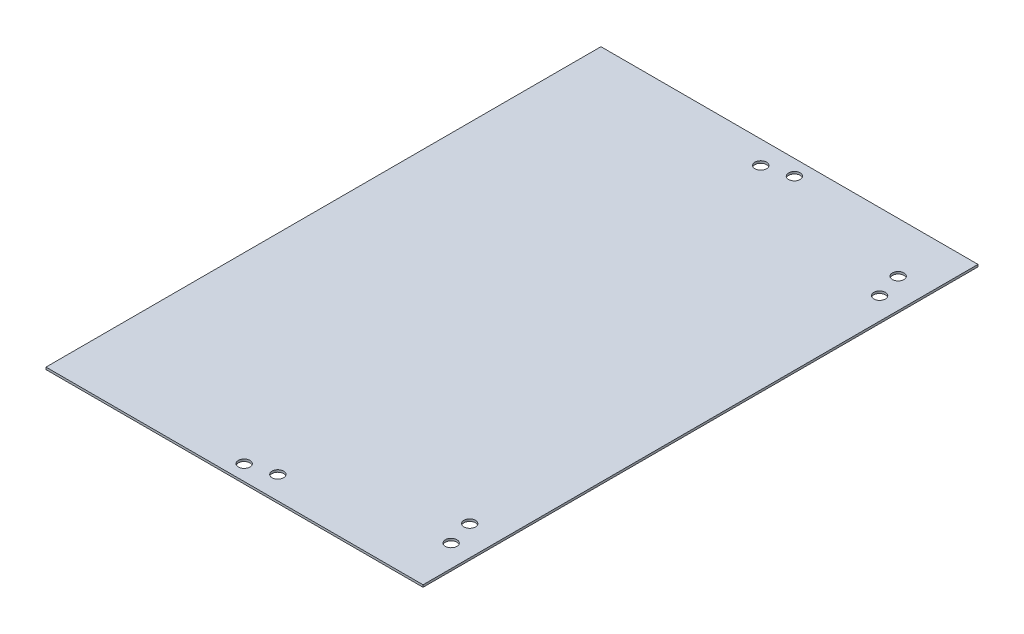
SolidWorks part; units mm, degrees
material "Alumina"
ref_plane "Front Plane" through (0, 0, 0) normal (0, 0, 1) x (1, 0, 0)
ref_plane "Top Plane" through (0, 0, 0) normal (0, 1, 0) x (1, 0, 0)
ref_plane "Right Plane" through (0, 0, 0) normal (1, 0, 0) x (0, 0, -1)
sketch "Sketch3" plane through (0, 0, 0) normal (0, 1, 0) x (1, 0, 0)
  line L1 (-110, 161.9) -> (110, 161.9)
  line L2 (-110, 161.9) -> (-110, -161.9)
  line L3 (-110, -161.9) -> (110, -161.9)
  line L4 (110, 161.9) -> (110, -161.9)
  line L5 (-110, 161.9) -> (110, -161.9) construction
  line L6 (-110, -161.9) -> (110, 161.9) construction
  point P0 (0, 0)
  dimension "D1" = 323.8
  dimension "D2" = 220
extrude "Boss-Extrude1" add sketch "Sketch3" along normal blind 1.2954
sketch "Sketch4" plane through (0, 1.2954, 0) normal (0, 1, 0) x (1, 0, 0)
  circle A0 centre (97.1046, -132.62) radius 3.3782
  circle A1 centre (92.7046, -117.38) radius 3.3782
  circle A2 centre (11.8746, -148.5) radius 3.3782
  circle A3 centre (-3.3654, -152.9) radius 3.3782
  circle A4 centre (97.1046, 117.38) radius 3.3782
  circle A6 centre (92.7046, 132.62) radius 3.3782
  circle A7 centre (11.8746, 152.9) radius 3.3782
  circle A8 centre (-3.3654, 148.5) radius 3.3782
extrude "Cut-Extrude1" cut sketch "Sketch4" against normal up to next
